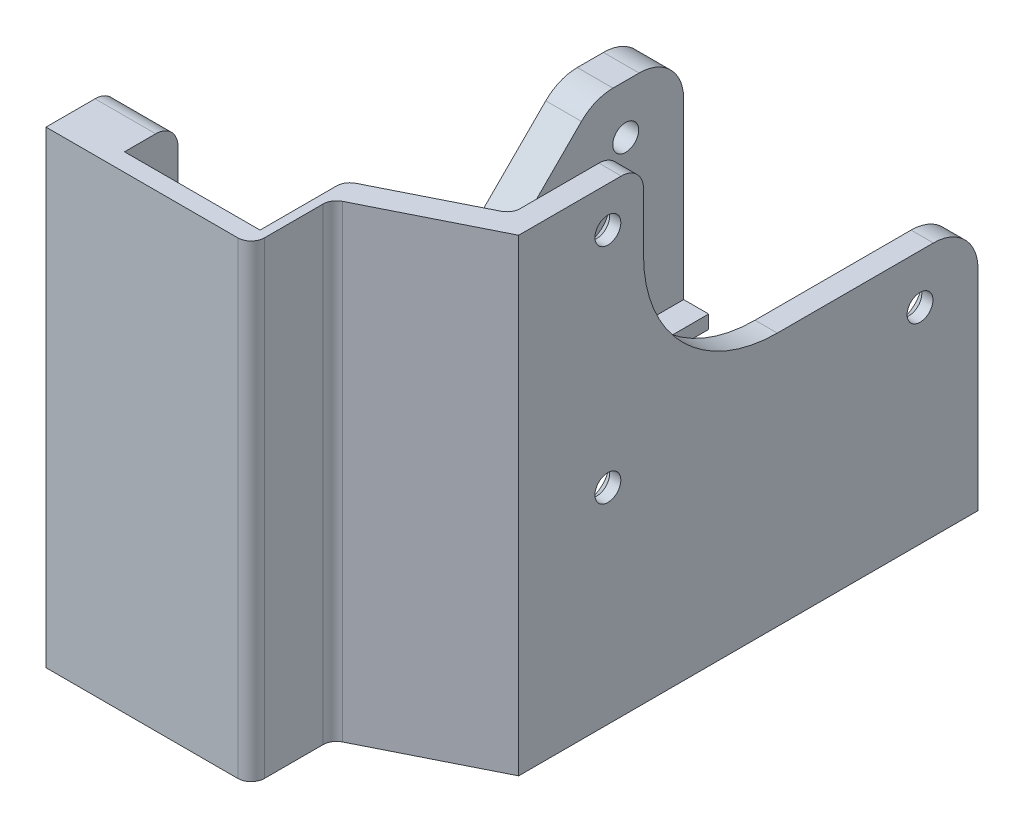
SolidWorks part; units mm, degrees
ref_plane "Спереди" through (0, 0, 0) normal (0, 0, 1) x (1, 0, 0)
ref_plane "Сверху" through (0, 0, 0) normal (0, 1, 0) x (1, 0, 0)
ref_plane "Справа" through (0, 0, 0) normal (1, 0, 0) x (0, 0, -1)
sketch "Эскиз2" plane through (0, 0, 0) normal (0, 1, 0) x (1, 0, 0)
  line L0 (0, -287.0595) -> (0, 0) construction
  line L1 (0, 0) -> (65.4832, 0) construction
  line L2 (52.3789, 0) -> (52.3789, -103)
  line L3 (52.3789, -103) -> (24.3789, -117)
  line L4 (24.3789, -117) -> (24.3789, -135)
  line L5 (24.3789, -135) -> (0, -135)
  line L8 (22.3789, 0) -> (22.3789, -131)
  line L9 (22.3789, -131) -> (0, -131)
  line L10 (0, -131) -> (-8.0211, -131)
  line L11 (-8.0211, -131) -> (-8.0211, 0)
  line L12 (-8.0211, 0) -> (-21.6211, 0)
  line L13 (-21.6211, 0) -> (-21.6211, -135)
  line L14 (-21.6211, -135) -> (0, -135)
  line L15 (22.3789, 0) -> (52.3789, 0)
  line L16 (-8.0211, -17.3266) -> (22.3789, -17.3266) construction
  line L17 (7.1789, -17.3266) -> (7.1789, 8.9751) construction
  dimension "D2" = 4
  dimension "D3" = 2
  dimension "D4" = 32
  dimension "D5" = 28
  dimension "D6" = 135
  dimension "D7" = 18
  dimension "D8" = 74
  dimension "D9" = 103
  dimension "D10" = 13.6
  dimension "D11" = 30.4
  dimension "D12" = 28.8
  dimension "D13" = 63.435
extrude "Бобышка-Вытянуть1" add sketch "Эскиз2" along normal blind 105
sketch "Эскиз4" plane through (0, 0, 0) normal (0, -1, 0) x (1, 0, 0)
  line L0 (-21.6211, 0) -> (52.3789, 0)
  line L1 (52.3789, 0) -> (52.3789, 103)
  line L2 (52.3789, 103) -> (24.3789, 117)
  line L3 (24.3789, 117) -> (24.3789, 135)
  line L4 (24.3789, 135) -> (-21.6211, 135)
  line L5 (-21.6211, 135) -> (-21.6211, 0)
sketch "Эскиз7" plane through (0, 0, 0) normal (0, -1, 0) x (1, 0, 0)
  line L0 (22.3789, 0) -> (22.3789, 131) construction
  line L1 (-8.0211, 131) -> (22.3789, 131)
  line L2 (-8.0211, 131) -> (-8.0211, 112)
  line L3 (-8.0211, 112) -> (22.3789, 112)
  line L4 (22.3789, 131) -> (22.3789, 112)
  dimension "D1" = 19
extrude "Бобышка-Вытянуть2" add sketch "Эскиз7" against normal blind 3 separate body
sketch "Эскиз8" plane through (0, 3, 0) normal (0, 1, 0) x (1, 0, 0)
  line L0 (-8.0211, -131) -> (-8.0211, -112) construction
  line L1 (22.3789, -131) -> (-8.0211, -131)
  line L2 (22.3789, -131) -> (22.3789, -119)
  line L3 (22.3789, -119) -> (-8.0211, -119)
  line L4 (-8.0211, -131) -> (-8.0211, -119)
  dimension "D1" = 12
extrude "Бобышка-Вытянуть3" add sketch "Эскиз8" along normal blind 38
fillet "Скругление1" radius 5 1 edges at (7.1789, 41, 119)
sketch "Эскиз3" plane through (0, 0, 0) normal (0, 0, -1) x (-1, 0, 0)
  line L0 (8.0211, -1.66) -> (19.3211, 3.4)
  line L1 (19.3211, 3.4) -> (19.3211, 5)
  line L2 (19.3211, 5) -> (8.0211, 5)
  line L3 (8.0211, 105) -> (8.0211, 0) construction
  line L4 (8.0211, 5) -> (8.0211, -1.66)
  line L5 (-7.1789, 0) -> (-7.1789, 26.9133) construction
  line L6 (-22.3789, 0) -> (8.0211, 0) construction
  line L7 (-33.6789, 5) -> (-22.3789, 5)
  line L8 (-33.6789, 3.4) -> (-33.6789, 5)
  line L9 (-22.3789, -1.66) -> (-33.6789, 3.4)
  line L10 (-22.3789, 5) -> (-22.3789, -1.66)
  line L11 (-24.3789, 0) -> (21.6211, 0) construction
  dimension "D1" = 6.66
  dimension "D2" = 1.6
  dimension "D3" = 5
  dimension "D4" = 53
  dimension "D5" = 15.2
  dimension "D6" = 15.2
  dimension "D7" = 11.3
extrude "Вырез-Вытянуть1" cut sketch "Эскиз3" against normal up to surface (112 mm away) up to face at (7.1789, 1.5, 112)
sketch "Эскиз9" plane through (0, 105, 0) normal (0, 1, 0) x (1, 0, 0)
  line L0 (-21.6211, 0) -> (-21.6211, -91)
  line L1 (-21.6211, 0) -> (52.3789, 0) construction
  line L2 (-21.6211, -91) -> (22.3789, -91)
  line L3 (22.3789, 0) -> (22.3789, -131) construction
  line L4 (22.3789, -119) -> (22.3789, -124) construction
  line L5 (22.3789, -91) -> (22.3789, -112)
  line L6 (-8.0211, -112) -> (22.3789, -112) construction
  line L7 (22.3789, -112) -> (47.3789, -99.5)
  line L8 (47.3789, -99.5) -> (47.3789, 0)
  line L9 (47.3789, 0) -> (-21.6211, 0)
  line L10 (22.3789, -131) -> (-8.0211, -131) construction
  line L13 (52.3789, 0) -> (52.3789, -103) construction
  line L14 (52.3789, -103) -> (24.3789, -117) construction
  dimension "D1" = 40
  dimension "D2" = 5.3666
  dimension "D3" = 5
extrude "Вырез-Вытянуть2" cut sketch "Эскиз9" against normal offset from surface (97 mm away) 3 up to face at (28.0289, 5, 56)
sketch "Эскиз11" plane through (-21.6211, 0, 0) normal (-1, 0, 0) x (0, 0, 1)
  line L0 (98.6, 88.4738) -> (98.6, 19.9227) construction
  line L1 (117, 0) -> (135, 0) construction
  line L2 (135, 105) -> (135, 0) construction
  circle A0 centre (98.6, 41.2) radius 5
  dimension "D2" = 10
  dimension "D3" = 41.2
  dimension "D4" = 36.4
extrude "Вырез-Вытянуть4" cut sketch "Эскиз11" against normal blind 6.8 and the other way through all
fillet "Скругление3" radius 3 4 edges at (47.3789, 56.5, 99.5) (24.3789, 52.5, 117) (24.3789, 52.5, 135) (22.3789, 56.5, 112)
sketch "Эскиз12" plane through (-21.6211, 0, 0) normal (-1, 0, 0) x (0, 0, 1)
  circle A0 centre (98.6, 41.2) radius 2.6
  dimension "D1" = 5.2
extrude "Вырез-Вытянуть5" cut sketch "Эскиз12" against normal blind 20
chamfer "Фаска1" distance 3 angle 45 1 edges at (-14.8211, 41.2, 101.2)
sketch "Эскиз13" plane through (-21.6211, 0, 0) normal (-1, 0, 0) x (0, 0, 1)
  line L0 (135, 105) -> (135, 0) construction
  line L1 (33.0864, 46) -> (83, 46) construction
  line L2 (83, 46) -> (83, 141.3627) construction
  line L3 (0, 0) -> (103, 0) construction
  circle A0 centre (83, 46) radius 2.9
  circle A1 centre (13, 46) radius 2.9
  circle A3 centre (83, 96) radius 2.9
  dimension "D1" = 5.8
  dimension "D2" = 50
  dimension "D3" = 70
  dimension "D4" = 52
  dimension "D5" = 46
  dimension "D6" = 20
extrude "Вырез-Вытянуть6" cut sketch "Эскиз13" against normal through all
chamfer "Фаска3" distance 2.5 angle 45 3 edges at (47.3789, 46, 10.1) (47.3789, 46, 80.1) (47.3789, 96, 80.1)
sketch "Эскиз16" plane through (-21.6211, 0, 0) normal (-1, 0, 0) x (0, 0, 1)
  line L0 (75, 105) -> (75, 57)
  line L1 (91, 105) -> (135, 105) construction
  line L2 (75, 57) -> (0, 57)
  line L3 (0, 8) -> (0, 0) construction
  line L4 (0, 57) -> (0, 105)
  line L5 (0, 105) -> (75, 105)
  line L6 (135, 105) -> (135, 0) construction
  dimension "D1" = 60
  dimension "D2" = 48
extrude "Вырез-Вытянуть9" cut sketch "Эскиз16" against normal through all
fillet "Скругление4" radius 30 1 edges at (49.8789, 57, 75)
sketch "Эскиз17" plane through (-21.6211, 0, 0) normal (-1, 0, 0) x (0, 0, 1)
  line L0 (91, 105) -> (135, 105) construction
  line L1 (119, 105) -> (91, 105)
  line L2 (119, 105) -> (119, 53)
  line L3 (119, 53) -> (91, 53)
  line L4 (91, 105) -> (91, 53)
  line L5 (91, 8) -> (91, 105) construction
  line L6 (135, 105) -> (135, 0) construction
  dimension "D1" = 16
  dimension "D2" = 52
extrude "Вырез-Вытянуть10" cut sketch "Эскиз17" against normal blind 20
fillet "Скругление5" radius 8 2 edges at (-14.8211, 53, 119) (-14.8211, 53, 91)
sketch "Эскиз18" plane through (0, 8, 0) normal (0, 1, 0) x (1, 0, 0)
  line L0 (-21.6211, -135) -> (-21.6211, 0) construction
  line L1 (-13.6211, -19) -> (-21.6211, -19)
  line L2 (-13.6211, -19) -> (-13.6211, 0)
  line L3 (-13.6211, 0) -> (-21.6211, 0)
  line L4 (-21.6211, -19) -> (-21.6211, 0)
  line L5 (24.3789, -135) -> (-21.6211, -135) construction
  dimension "D1" = 8
  dimension "D3" = 116
extrude "Бобышка-Вытянуть4" add sketch "Эскиз18" along normal up to surface (49 mm away) up to face at (49.8789, 57, 22.5)
chamfer "Фаска4" distance 50 angle 45 1 edges at (-17.6211, 8, 19)
fillet "Скругление6" radius 10 2 edges at (49.8789, 57, 0) (-17.6211, 57, 0)
sketch "Эскиз19" plane through (52.3789, 0, 0) normal (1, 0, 0) x (0, 0, -1)
  circle A0 centre (-13, 46) radius 2.9
extrude "Вырез-Вытянуть11" cut sketch "Эскиз19" against normal through all
chamfer "Фаска5" distance 2.6 angle 45 1 edges at (-21.6211, 46, 10.1)
sketch "Эскиз21" plane through (-21.6211, 0, 0) normal (-1, 0, 0) x (0, 0, 1)
  line L0 (125, 108.683) -> (125, -7.686) construction
  line L1 (135, 105) -> (135, 0) construction
  line L2 (117, 0) -> (135, 0) construction
  circle A0 centre (125, 30) radius 2.3
  circle A1 centre (125, 90) radius 2.3
  dimension "D2" = 4.6
  dimension "D3" = 60
  dimension "D1" = 10
  dimension "D4" = 30
extrude "Вырез-Вытянуть13" cut sketch "Эскиз21" against normal blind 15
fillet "Скругление7" radius 5 2 edges at (-14.8211, 105, 119) (49.8789, 105, 75)
chamfer "Фаска6" distance 0.8 angle 45 3 edges at (-21.6211, 41.2, 93.6) (-21.6211, 30, 127.3) (-21.6211, 90, 127.3)
sketch "Эскиз22" plane through (0, 8, 0) normal (0, 1, 0) x (1, 0, 0)
  line L0 (-13.6211, -20) -> (-13.6211, -69) construction
  line L1 (-21.6211, -91) -> (-13.6211, -91)
  line L2 (-21.6211, -91) -> (-21.6211, -47.3162)
  line L3 (-21.6211, -47.3162) -> (-13.6211, -47.3162)
  line L4 (-13.6211, -91) -> (-13.6211, -47.3162)
  line L5 (-13.6211, -69) -> (-13.6211, 0) construction
extrude "Бобышка-Вытянуть5" add sketch "Эскиз22" along normal blind 10
fillet "Скругление8" radius 10 1 edges at (-17.6211, 57, 20)
